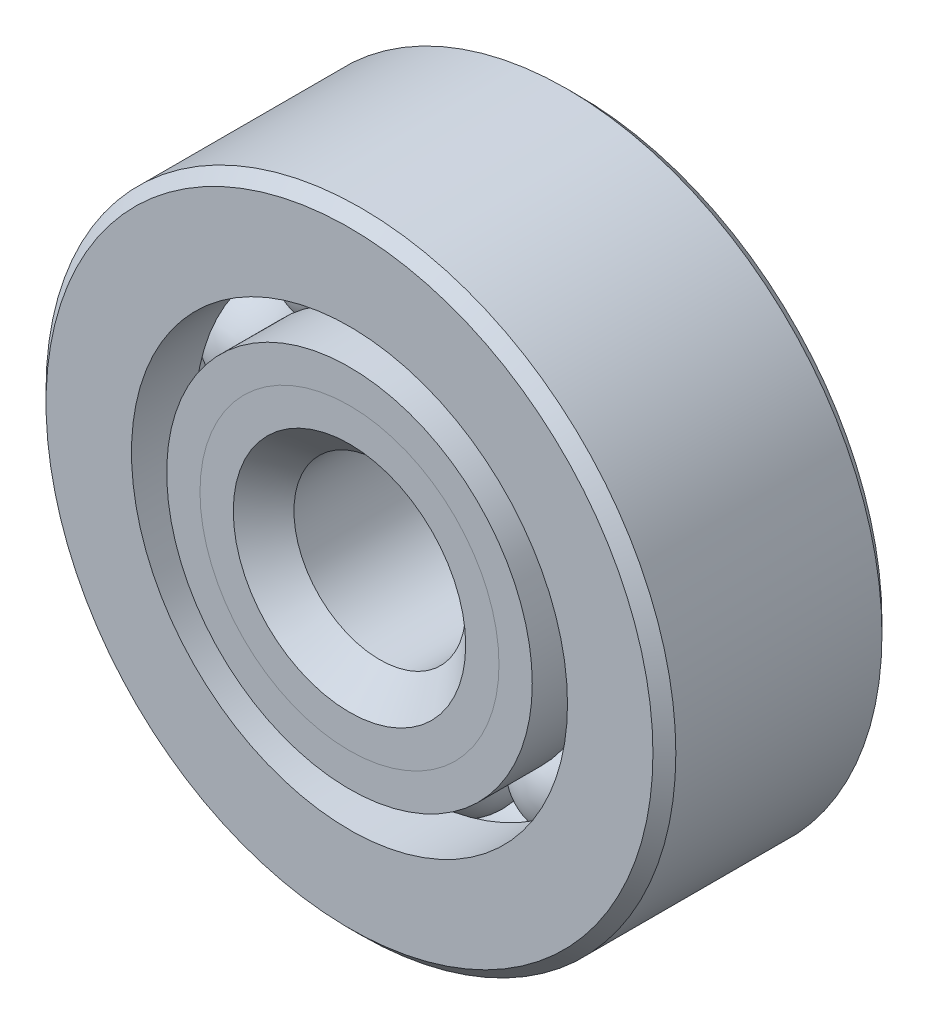
SolidWorks part; units mm, degrees
ref_plane "Front Plane" through (0, 0, 0) normal (0, 0, 1) x (1, 0, 0)
ref_plane "Top Plane" through (0, 0, 0) normal (0, 1, 0) x (1, 0, 0)
ref_plane "Right Plane" through (0, 0, 0) normal (1, 0, 0) x (0, 0, -1)
sketch "Sketch1" plane through (0, 0, 0) normal (1, 0, 0) x (0, 0, -1)
  line L0 (-3.175, 0) -> (3.175, 0) construction
  line L1 (0, 8.7312) -> (0, -8.7312) construction
  line L2 (2.8575, 8.7312) -> (-2.8575, 8.7312)
  line L3 (-2.8575, 8.7312) -> (-3.175, 8.4137)
  line L4 (-3.175, 8.4137) -> (-3.175, 6.0447)
  line L5 (-3.175, 6.0447) -> (-1.4111, 6.0447)
  line L6 (3.175, 6.0447) -> (1.4111, 6.0447)
  line L7 (3.175, 8.4137) -> (3.175, 6.0447)
  line L8 (2.8575, 8.7312) -> (3.175, 8.4137)
  line L9 (0, 8.7312) -> (0, 5.5562) construction
  line L10 (0, 5.5562) -> (0, 2.3812) construction
  arc A0 (-1.4111, 6.0447) -> (1.4111, 6.0447) centre (0, 5.5562) cw
  point P14 (0, 2.3812)
  dimension "D3" = 2.8222
  dimension "D1" = 45
  dimension "Width" = 6.35
  dimension "OD" = 17.4625
  dimension "D2" = 0.3175
  dimension "Shaft Dia" = 4.7625
  dimension "D4" = 0.4885
revolve "Revolve1" add sketch "Sketch1" angle 360 about L0
sketch "Sketch2" plane through (0, 0, 0) normal (1, 0, 0) x (0, 0, -1)
  line L0 (-3.175, 5.0678) -> (-1.4111, 5.0678)
  line L1 (-3.175, 8.4137) -> (-3.175, -8.4137) construction
  line L2 (-3.175, 5.0678) -> (-3.175, 4.145)
  line L3 (-3.175, 4.145) -> (-2.2522, 3.2221)
  line L4 (-2.2522, 3.2221) -> (0, 3.2221)
  line L5 (0, 8.7312) -> (0, -8.7312) construction
  line L6 (0, 3.2221) -> (0, 4.063)
  line L7 (0, 4.063) -> (0, 2.3812) construction
  line L8 (-3.175, 5.0678) -> (-3.175, 3.2221) construction
  line L9 (-3.175, 3.2221) -> (-2.2522, 3.2221) construction
  arc A0 (-1.4111, 5.0678) -> (0, 4.063) centre (0, 5.5562) ccw
  arc A1 (1.4111, 6.0447) -> (-1.4111, 6.0447) centre (0, 5.5562) ccw construction
  circle A2 centre (0, 5.5562) radius 1.4933 construction
  dimension "D1" = 45
revolve "Revolve2" add sketch "Sketch2" angle 360 about L0
sketch "Sketch3" plane through (0, 0, 0) normal (1, 0, 0) x (0, 0, -1)
  line L0 (-3.175, 4.145) -> (-2.2522, 3.2221)
  line L1 (-2.2522, 3.2221) -> (0, 3.2221)
  line L2 (0, 3.2221) -> (0, 4.063)
  line L3 (-3.175, 4.145) -> (-3.175, 3.2221)
  line L4 (-3.175, 5.0678) -> (-3.175, 3.2221) construction
  line L5 (-3.175, 3.2221) -> (-2.3341, 2.3812)
  line L6 (-2.3341, 2.3812) -> (2.8575, 2.3812)
  line L7 (2.8575, 8.7312) -> (2.8575, -8.7312) construction
  line L8 (2.8575, 2.3812) -> (3.175, 2.6988)
  line L9 (3.175, -8.4137) -> (3.175, 8.4137) construction
  line L10 (3.175, 2.6988) -> (3.175, 5.0678)
  line L11 (3.175, 5.0678) -> (1.4111, 5.0678)
  line L13 (2.8575, 8.7312) -> (3.175, 8.4137) construction
  circle A0 centre (0, 5.5562) radius 1.4933 construction
  arc A1 (1.4111, 5.0678) -> (0, 4.063) centre (0, 5.5562) cw
revolve "Revolve3" add sketch "Sketch3" angle 360 about L0
sketch "Sketch4" plane through (0, 0, 0) normal (1, 0, 0) x (0, 0, -1)
  line L0 (-1.4933, 5.5562) -> (1.4933, 5.5562)
  circle A1 centre (0, 5.5562) radius 1.4933 construction
  arc A2 (-1.4933, 5.5562) -> (1.4933, 5.5562) centre (0, 5.5562) cw
  arc A3 (1.4111, 6.0447) -> (-1.4111, 6.0447) centre (0, 5.5562) ccw construction
revolve "Revolve4" add sketch "Sketch4" angle 360 about L0
ref_axis "Axis1" through (0, 0, -3.175) along (0, 0, 1)
pattern_circular "CirPattern1" count 10 every 36 about axis through (0, 0, -3.175) along (0, 0, 1) of bodies 104
equation "\"D2@Sketch1\" = \"Width@Sketch1\"*.05"
equation "\"D3@Sketch1\" = \"Width@Sketch1\"/2.25"
equation "\"D4@Sketch1\" = (((\"OD@Sketch1\"-\"Width@Sketch1\")/2)/3.25)/3.5"
equation "\"D2@CirPattern1\" = 360/\"Balls@CirPattern1\""
